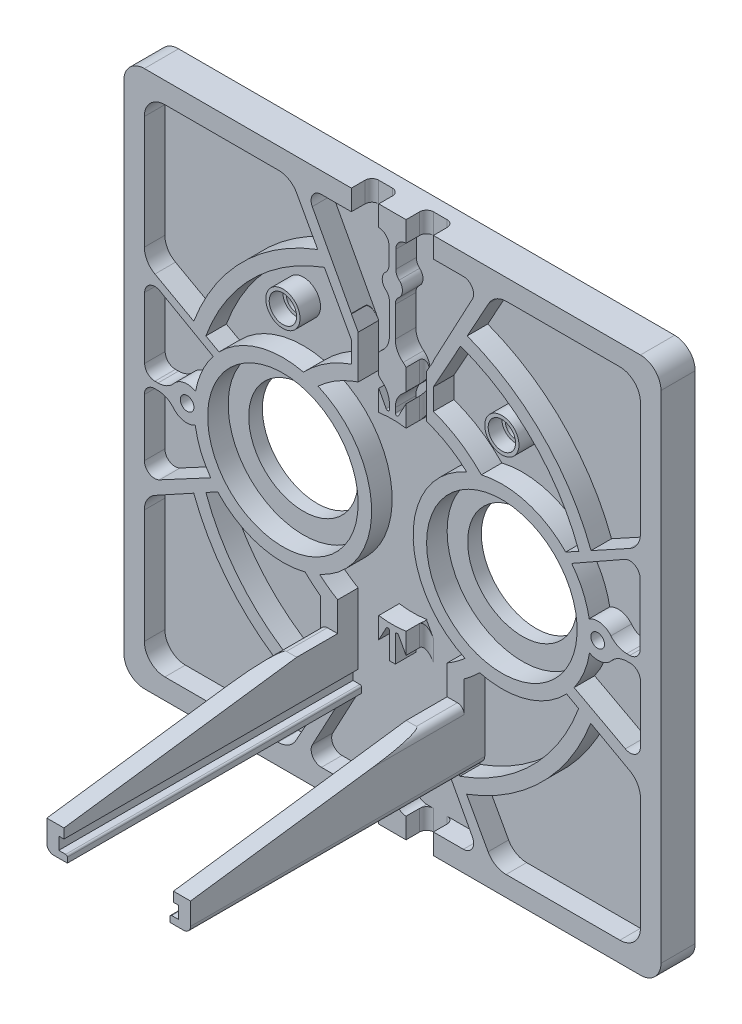
SolidWorks part; units mm, degrees
ref_plane "Спереди" through (0, 0, 0) normal (0, 0, 1) x (1, 0, 0)
ref_plane "Сверху" through (0, 0, 0) normal (0, 1, 0) x (1, 0, 0)
ref_plane "Справа" through (0, 0, 0) normal (1, 0, 0) x (0, 0, -1)
sketch "Эскиз1" plane through (0, 0, 0) normal (0, 0, 1) x (1, 0, 0)
  line L5 (-36.25, -39.25) -> (36.25, -39.25)
  line L6 (-39.25, -36.25) -> (-39.25, 36.25)
  line L7 (-36.25, 39.25) -> (36.25, 39.25)
  line L8 (39.25, -36.25) -> (39.25, 36.25)
  arc A0 (-36.25, -39.25) -> (-39.25, -36.25) centre (-36.25, -36.25) cw
  arc A1 (36.25, -39.25) -> (39.25, -36.25) centre (36.25, -36.25) ccw
  arc A2 (36.25, 39.25) -> (39.25, 36.25) centre (36.25, 36.25) cw
  arc A3 (-39.25, 36.25) -> (-36.25, 39.25) centre (-36.25, 36.25) cw
  dimension "D1" = 3
extrude "Бобышка-Вытянуть2" add sketch "Эскиз1" along normal blind 5
sketch "Эскиз6" plane through (0, 0, 5) normal (0, 0, 1) x (1, 0, 0)
  circle A0 centre (0, 0) radius 13
extrude "Вырез-Вытянуть2" cut sketch "Эскиз6" against normal blind 3
sketch "Эскиз10" plane through (0, 0, 5) normal (0, 0, 1) x (1, 0, 0)
  line L10 (-36.25, -33.25) -> (-36.25, -16.6195)
  line L11 (-33.25, -36.25) -> (-16.7128, -36.25)
  line L12 (-34.6933, -13.9895) -> (-12.8452, -2)
  line L13 (-14.0876, -34.7019) -> (-2, -12.8452)
  line L14 (-2, -12.8452) -> (-12.8452, -2)
  line L15 (36.2485, 33.2453) -> (36.2485, 16.6148)
  line L16 (33.2485, 36.2453) -> (16.7113, 36.2453)
  line L17 (34.6917, 13.9847) -> (12.8437, 1.9953)
  line L18 (14.086, 34.6972) -> (1.9985, 12.8405)
  line L19 (1.9985, 12.8405) -> (12.8437, 1.9953)
  line L20 (33.2453, -36.3173) -> (16.6148, -36.3173)
  line L21 (36.2453, -33.3173) -> (36.2453, -16.7802)
  line L22 (13.9847, -34.7606) -> (1.9953, -12.9126)
  line L23 (34.6972, -14.1549) -> (12.8405, -2.0673)
  line L24 (12.8405, -2.0673) -> (1.9953, -12.9126)
  line L25 (-33.25, 36.1811) -> (-16.6195, 36.1811)
  line L26 (-36.25, 33.1811) -> (-36.25, 16.644)
  line L27 (-13.9895, 34.6244) -> (-2, 12.7764)
  line L28 (-34.7019, 14.0187) -> (-12.8452, 1.9311)
  line L29 (-12.8452, 1.9311) -> (-2, 12.7764)
  circle A0 centre (0, 0) radius 13 construction
  arc A1 (-36.25, -16.6195) -> (-34.6933, -13.9895) centre (-33.25, -16.6195) cw
  arc A2 (-16.7128, -36.25) -> (-14.0876, -34.7019) centre (-16.7128, -33.25) ccw
  arc A3 (-36.25, -33.25) -> (-33.25, -36.25) centre (-33.25, -33.25) ccw
  arc A4 (36.2485, 16.6148) -> (34.6917, 13.9847) centre (33.2485, 16.6148) cw
  arc A5 (16.7113, 36.2453) -> (14.086, 34.6972) centre (16.7113, 33.2453) ccw
  arc A6 (36.2485, 33.2453) -> (33.2485, 36.2453) centre (33.2485, 33.2453) ccw
  arc A7 (16.6148, -36.3173) -> (13.9847, -34.7606) centre (16.6148, -33.3173) cw
  arc A8 (36.2453, -16.7802) -> (34.6972, -14.1549) centre (33.2453, -16.7802) ccw
  arc A9 (33.2453, -36.3173) -> (36.2453, -33.3173) centre (33.2453, -33.3173) ccw
  arc A10 (-16.6195, 36.1811) -> (-13.9895, 34.6244) centre (-16.6195, 33.1811) cw
  arc A11 (-36.25, 16.644) -> (-34.7019, 14.0187) centre (-33.25, 16.644) ccw
  arc A12 (-33.25, 36.1811) -> (-36.25, 33.1811) centre (-33.25, 33.1811) ccw
  point P34 (-36.25, -36.25)
  dimension "D1" = 3
extrude "Вырез-Вытянуть4" cut sketch "Эскиз10" against normal blind 3
sketch "Эскиз12" plane through (0, 0, 2) normal (0, 0, 1) x (1, 0, 0)
  circle A0 centre (0, 0) radius 18
  circle A1 centre (0, 0) radius 16
extrude "Бобышка-Вытянуть7" add sketch "Эскиз12" along normal blind 3
sketch "Эскиз18" plane through (0, 0, 2) normal (0, 0, 1) x (1, 0, 0)
  circle A0 centre (0, 0) radius 29
  circle A1 centre (0, 0) radius 31
extrude "Бобышка-Вытянуть10" add sketch "Эскиз18" along normal blind 3
sketch "Эскиз19" plane through (0, 0, 2) normal (0, 0, 1) x (1, 0, 0)
  circle A0 centre (-30, 0) radius 1
  circle A1 centre (30, 0) radius 1
extrude "Вырез-Вытянуть7" cut sketch "Эскиз19" against normal blind 2 and the other way blind 3
chamfer "Фаска6" distance 2 angle 45 2 edges at (-29, 0, 0) (31, 0, 0)
sketch "Эскиз21" plane through (0, 0, 5) normal (0, 0, 1) x (1, 0, 0)
  line L0 (-34.7046, 0.4543) -> (-34.2543, 0.4543)
  line L14 (-25.7046, 0.3762) -> (-13.9439, 0.3789)
  line L17 (-25.761, -0.4346) -> (-13.9898, -0.4346)
  line L18 (-33.9662, 12.24) -> (-13.8209, 0.8465)
  line L19 (-36.2046, 1.9543) -> (-36.2046, 10.9344)
  line L22 (-0.495, -34.7501) -> (-0.495, -32.2046)
  line L23 (-36.25, -2.0051) -> (-36.25, -10.3806)
  line L24 (-34.0421, -11.703) -> (-13.8718, -0.905)
  line L25 (-34.75, -0.5051) -> (-34.2952, -0.5051)
  line L26 (-0.4246, -27.7337) -> (-0.4246, -13.9898)
  line L27 (0.4345, -27.7337) -> (0.4345, -13.9898)
  line L28 (-11.693, -34.0421) -> (-0.895, -13.8718)
  line L29 (-1.995, -36.2501) -> (-10.3705, -36.2501)
  line L30 (2.005, -36.2501) -> (10.3805, -36.2501)
  line L31 (11.7029, -34.0421) -> (0.9049, -13.8718)
  line L32 (0.505, -34.7501) -> (0.505, -32.2046)
  line L38 (0.4928, 34.7538) -> (0.4928, 32.2084)
  line L44 (11.6908, 34.0458) -> (0.8928, 13.8756)
  line L45 (1.9928, 36.2538) -> (10.3683, 36.2538)
  line L46 (-2.0072, 36.2538) -> (-10.3827, 36.2538)
  line L47 (-11.7051, 34.0459) -> (-0.9071, 13.8756)
  line L48 (-0.5072, 34.7538) -> (-0.5072, 32.2084)
  line L50 (-0.4367, 13.9936) -> (-0.4367, 14.7298)
  line L51 (0.4224, 13.9936) -> (0.4224, 14.6764)
  line L52 (0.4224, 27.7375) -> (0.4224, 23.3236)
  line L53 (-0.4367, 27.7375) -> (-0.4367, 23.2702)
  line L54 (34.75, -0.5051) -> (34.2952, -0.5051)
  line L55 (36.25, -2.0051) -> (36.25, -10.3806)
  line L56 (34.0421, -11.703) -> (13.8718, -0.905)
  line L57 (25.761, -0.4346) -> (13.9898, -0.4346)
  line L58 (34.7046, 0.4543) -> (34.2543, 0.4543)
  line L59 (36.2046, 1.9543) -> (36.2046, 10.9344)
  line L60 (33.9662, 12.24) -> (13.8209, 0.8465)
  line L61 (25.7046, 0.3762) -> (13.9439, 0.3789)
  arc A8 (-12.855, 1.9365) -> (-12.8452, -2) centre (0, 0) ccw construction
  arc A9 (-12.855, 1.9365) -> (-12.8452, -2) centre (0, 0) ccw construction
  arc A15 (-36.25, -10.3806) -> (-34.0421, -11.703) centre (-34.75, -10.3806) ccw
  arc A16 (-36.25, -2.0051) -> (-34.75, -0.5051) centre (-34.75, -2.0051) cw
  arc A17 (-36.2046, 10.9344) -> (-33.9662, 12.24) centre (-34.7046, 10.9344) cw
  arc A18 (-36.2046, 1.9543) -> (-34.7046, 0.4543) centre (-34.7046, 1.9543) ccw
  arc A19 (-13.9898, -0.4346) -> (-13.8718, -0.905) centre (-13.9898, -0.6846) cw
  arc A20 (-13.9439, 0.3789) -> (-13.8209, 0.8465) centre (-13.944, 0.6289) ccw
  arc A22 (0.9636, -28.8771) -> (0.9985, -31.0924) centre (0.01, -30.0001) cw
  arc A23 (-0.9537, -28.8771) -> (-0.9886, -31.0924) centre (-0.0001, -30.0001) ccw
  arc A24 (-0.9886, -31.0924) -> (-0.495, -32.2046) centre (-1.995, -32.2046) cw
  arc A25 (-0.4246, -27.7337) -> (-0.9537, -28.8771) centre (-1.9246, -27.7337) cw
  arc A26 (0.4345, -27.7337) -> (0.9636, -28.8771) centre (1.9345, -27.7337) ccw
  arc A27 (0.9985, -31.0924) -> (0.505, -32.2046) centre (2.005, -32.2046) ccw
  arc A28 (10.3805, -36.2501) -> (11.7029, -34.0421) centre (10.3805, -34.7501) ccw
  arc A29 (2.005, -36.2501) -> (0.505, -34.7501) centre (2.005, -34.7501) cw
  arc A30 (-10.3705, -36.2501) -> (-11.693, -34.0421) centre (-10.3705, -34.7501) cw
  arc A31 (-1.995, -36.2501) -> (-0.495, -34.7501) centre (-1.995, -34.7501) ccw
  arc A32 (0.4345, -13.9898) -> (0.9049, -13.8718) centre (0.6845, -13.9898) cw
  arc A33 (-0.4246, -13.9898) -> (-0.895, -13.8718) centre (-0.6746, -13.9898) ccw
  arc A46 (-0.9658, 28.8809) -> (-1.0007, 31.0961) centre (-0.0122, 30.0038) cw
  arc A47 (0.9515, 28.8809) -> (0.9864, 31.0961) centre (-0.0021, 30.0038) ccw
  arc A48 (0.9864, 31.0961) -> (0.4928, 32.2084) centre (1.9928, 32.2084) cw
  arc A49 (0.4224, 27.7375) -> (0.9515, 28.8809) centre (1.9224, 27.7375) cw
  arc A50 (-0.4367, 27.7375) -> (-0.9658, 28.8809) centre (-1.9367, 27.7375) ccw
  arc A51 (-1.0007, 31.0961) -> (-0.5072, 32.2084) centre (-2.0072, 32.2084) ccw
  arc A52 (-10.3827, 36.2538) -> (-11.7051, 34.0459) centre (-10.3827, 34.7538) ccw
  arc A53 (-2.0072, 36.2538) -> (-0.5072, 34.7538) centre (-2.0072, 34.7538) cw
  arc A54 (10.3683, 36.2538) -> (11.6908, 34.0458) centre (10.3683, 34.7538) cw
  arc A55 (1.9928, 36.2538) -> (0.4928, 34.7538) centre (1.9928, 34.7538) ccw
  arc A56 (-0.4367, 13.9936) -> (-0.9071, 13.8756) centre (-0.6867, 13.9936) cw
  arc A57 (0.4224, 13.9936) -> (0.8928, 13.8756) centre (0.6724, 13.9936) ccw
  arc A60 (-1.542, 17.0558) -> (-1.542, 20.9442) centre (0.0417, 19) cw
  arc A61 (1.5709, 17.0369) -> (1.5709, 20.9631) centre (0.0311, 19) ccw
  arc A62 (0.4224, 14.6764) -> (1.5709, 17.0369) centre (3.4224, 14.6764) cw
  arc A63 (-0.4367, 14.7298) -> (-1.542, 17.0558) centre (-3.4367, 14.7298) ccw
  arc A64 (0.4224, 23.3236) -> (1.5709, 20.9631) centre (3.4224, 23.3236) ccw
  arc A65 (-0.4367, 23.2702) -> (-1.542, 20.9442) centre (-3.4367, 23.2702) cw
  arc A67 (-31.94, 1.5454) -> (-28.0541, 1.5099) centre (-30.0114, -0.0454) cw
  arc A68 (-31.9834, -1.5932) -> (-28.1042, -1.5612) centre (-30.0568, 0) ccw
  arc A69 (-25.7046, 0.3762) -> (-28.0541, 1.5099) centre (-25.7053, 3.3762) cw
  arc A70 (-25.761, -0.4346) -> (-28.1042, -1.5612) centre (-25.761, -3.4346) ccw
  arc A71 (-34.2952, -0.5051) -> (-31.9834, -1.5932) centre (-34.2952, -3.5051) cw
  arc A72 (-34.2543, 0.4543) -> (-31.94, 1.5454) centre (-34.2543, 3.4543) ccw
  arc A73 (36.25, -2.0051) -> (34.75, -0.5051) centre (34.75, -2.0051) ccw
  arc A74 (36.25, -10.3806) -> (34.0421, -11.703) centre (34.75, -10.3806) cw
  arc A75 (13.9898, -0.4346) -> (13.8718, -0.905) centre (13.9898, -0.6846) ccw
  arc A76 (25.761, -0.4346) -> (28.1042, -1.5612) centre (25.761, -3.4346) cw
  arc A77 (34.2952, -0.5051) -> (31.9834, -1.5932) centre (34.2952, -3.5051) ccw
  arc A78 (31.9834, -1.5932) -> (28.1042, -1.5612) centre (30.0568, 0) cw
  arc A79 (36.2046, 1.9543) -> (34.7046, 0.4543) centre (34.7046, 1.9543) cw
  arc A80 (36.2046, 10.9344) -> (33.9662, 12.24) centre (34.7046, 10.9344) ccw
  arc A81 (13.9439, 0.3789) -> (13.8209, 0.8465) centre (13.944, 0.6289) cw
  arc A82 (25.7046, 0.3762) -> (28.0541, 1.5099) centre (25.7053, 3.3762) ccw
  arc A83 (34.2543, 0.4543) -> (31.94, 1.5454) centre (34.2543, 3.4543) cw
  arc A84 (31.94, 1.5454) -> (28.0541, 1.5099) centre (30.0114, -0.0454) ccw
  point P39 (-12.9945, 0.3791)
  point P148 (0.4224, 16.5359)
  point P151 (-0.4367, 16.5384)
  dimension "D1" = 3
  dimension "D2" = 0.25
  dimension "D3" = 3
extrude "Вырез-Вытянуть8" cut sketch "Эскиз21" against normal blind 3
sketch "Эскиз22" plane through (0, 48.4151, 2) normal (0, 0, 1) x (1, 0, 0)
  line L52 (-8.75, -74.3614) -> (-7.75, -74.3614)
  line L53 (-8.75, -72.5614) -> (-8.75, -74.3614)
  line L58 (-10.5, -67.5575) -> (-10.5, -71.5614)
  line L59 (-10.5, -71.5614) -> (-10.5, -72.0614)
  line L60 (-10.5, -74.3614) -> (-10.5, -72.0614)
  line L64 (-8.75, -72.5614) -> (-8, -72.5614)
  line L65 (-9.5, -75.3614) -> (-7.5, -75.3614)
  line L66 (-7.5, -75.3614) -> (-7.5, -74.6114)
  line L67 (-9.5, -66.5575) -> (-8, -66.5575)
  line L68 (-8, -66.5575) -> (-8, -72.5614)
  line L70 (9.5, -66.5575) -> (8, -66.5575)
  line L71 (10.5, -67.5575) -> (10.5, -71.5614)
  line L72 (10.5, -71.5614) -> (10.5, -72.0614)
  line L73 (10.5, -74.3614) -> (10.5, -72.0614)
  line L74 (9.5, -75.3614) -> (7.5, -75.3614)
  line L75 (7.5, -75.3614) -> (7.5, -74.6114)
  line L76 (8.75, -74.3614) -> (7.75, -74.3614)
  line L77 (8.75, -72.5614) -> (8.75, -74.3614)
  line L78 (8.75, -72.5614) -> (8, -72.5614)
  line L79 (8, -66.5575) -> (8, -72.5614)
  arc A18 (9.5, -66.5575) -> (10.5, -67.5575) centre (9.5, -67.5575) cw
  arc A26 (-7.75, -74.3614) -> (-7.5, -74.6114) centre (-7.75, -74.6114) cw
  arc A29 (-9.5, -66.5575) -> (-10.5, -67.5575) centre (-9.5, -67.5575) ccw
  arc A30 (-9.5, -75.3614) -> (-10.5, -74.3614) centre (-9.5, -74.3614) cw
  arc A31 (9.5, -75.3614) -> (10.5, -74.3614) centre (9.5, -74.3614) ccw
  arc A32 (7.75, -74.3614) -> (7.5, -74.6114) centre (7.75, -74.6114) ccw
  point P0 (0, 0)
sketch "Эскиз27" plane through (0, -39.25, 0) normal (0, -1, 0) x (-1, 0, 0)
  line L15 (36.25, -5) -> (-36.25, -5) construction
  line L17 (1.995, -5) -> (5.9932, -5)
  line L22 (5.9932, -5) -> (5.9932, -3)
  line L23 (4.9932, -2) -> (2.995, -2)
  line L24 (1.995, -3) -> (1.995, -5)
  line L29 (-1.995, -3) -> (-1.995, -5)
  line L30 (-4.9932, -2) -> (-2.995, -2)
  line L31 (-5.9932, -5) -> (-5.9932, -3)
  line L32 (-1.995, -5) -> (-5.9932, -5)
  arc A0 (2.995, -2) -> (1.995, -3) centre (2.995, -3) ccw
  arc A1 (5.9932, -3) -> (4.9932, -2) centre (4.9932, -3) ccw
  arc A4 (-2.995, -2) -> (-1.995, -3) centre (-2.995, -3) cw
  arc A5 (-5.9932, -3) -> (-4.9932, -2) centre (-4.9932, -3) cw
  dimension "D1" = 1
extrude "Вырез-Вытянуть12" cut sketch "Эскиз27" against normal blind 78.5
sketch "Эскиз28" plane through (0, 0, 2) normal (0, 0, 1) x (1, 0, 0)
  line L0 (-5.9932, -14.8352) -> (-5.9932, -23.3951)
  line L1 (-5.9932, -23.3951) -> (-4.9932, -21.5271)
  line L2 (-4.9932, -21.5271) -> (-4.9932, -15.2009)
  line L3 (-4.9932, -15.2009) -> (-5.9932, -14.8352)
  line L4 (5.9932, -14.8352) -> (5.9932, -23.3765)
  line L5 (5.9932, -23.3765) -> (4.9932, -21.5085)
  line L6 (4.9932, -21.5085) -> (4.9932, -15.2009)
  line L7 (4.9932, -15.2009) -> (5.9932, -14.8352)
  line L8 (-4.9932, 15.2009) -> (-4.9932, 21.5081)
  line L9 (-4.9932, 21.5081) -> (-5.9932, 23.3125)
  line L10 (-5.9932, 23.3761) -> (-5.9932, 20.053) construction
  line L11 (-5.9932, 23.3125) -> (-5.9932, 14.8352)
  line L12 (-5.9932, 14.8352) -> (-4.9932, 15.2009)
  line L13 (5.9932, 14.8352) -> (5.9932, 23.3125)
  line L14 (5.9932, 23.4029) -> (5.9932, 20.0637) construction
  line L15 (5.9932, 23.3125) -> (4.9932, 21.535)
  line L16 (4.9932, 21.535) -> (4.9932, 15.2009)
  line L17 (4.9932, 15.2009) -> (5.9932, 14.8352)
  arc A0 (-4.9932, 15.2009) -> (-15.6201, 3.4658) centre (0, 0) ccw construction
  arc A1 (-4.9932, 15.2009) -> (-5.9932, 14.8352) centre (0, 0) ccw construction
extrude "Бобышка-Вытянуть12" add sketch "Эскиз28" along normal blind 3
extrude "Бобышка-Вытянуть15" add sketch "Эскиз22" along normal blind 43
sketch "Эскиз36" plane through (-10.5, 0, 0) normal (-1, 0, 0) x (0, 0, 1)
  line L0 (48, -17.3606) -> (5.1996, -17.3606)
  line L2 (48, -19.1424) -> (48, -25.9463) construction
  line L3 (48, -23.1435) -> (48, -17.3606)
  line L4 (5.1996, -17.3606) -> (48, -23.1435)
extrude "Вырез-Вытянуть13" cut sketch "Эскиз36" against normal blind 22
sketch "Эскиз43" plane through (0, 0, 5) normal (0, 0, 1) x (1, 0, 0)
  line L2 (-7.5, -26.1963) -> (-7.5, -26.9463)
  line L3 (-7.5, -26.9463) -> (7.5, -26.9463)
  line L4 (7.5, -26.9463) -> (7.5, -26.1963)
  line L8 (8, -24.1463) -> (8, -13.0041)
  line L9 (8, -13.0041) -> (4.2218, -15.0228)
  line L10 (4.2218, -15.0228) -> (2.995, -17.7761)
  line L11 (2.995, -17.7761) -> (-2.995, -17.7947)
  line L12 (-2.995, -17.7947) -> (-4.6348, -13.8953)
  line L13 (-4.6348, -13.8953) -> (-8, -12.9987)
  line L14 (-8, -12.9987) -> (-8, -24.1463)
  line L16 (-8, -24.1463) -> (-8.75, -24.1463)
  line L17 (-8.75, -24.1463) -> (-8.75, -25.9463)
  line L18 (-8.75, -25.9463) -> (-7.75, -25.9463)
  line L19 (8, -24.1463) -> (8.75, -24.1463)
  line L20 (8.75, -24.1463) -> (8.75, -25.9463)
  line L21 (8.75, -25.9463) -> (7.75, -25.9463)
  arc A0 (7.5, -26.1963) -> (7.75, -25.9463) centre (7.75, -26.1963) cw
  arc A1 (-7.75, -25.9463) -> (-7.5, -26.1963) centre (-7.75, -26.1963) cw
  dimension "D1" = 0.25
extrude "Вырез-Вытянуть17" cut sketch "Эскиз43" against normal blind 3
sketch "Эскиз45" plane through (0, 0, 2) normal (0, 0, 1) x (1, 0, 0)
  line L0 (-10.5, -19.1424) -> (-8, -19.1424)
  line L1 (-8, -18.1424) -> (-8, -23.1435) construction
  line L2 (-8, -19.1424) -> (-8, -16.1245)
  line L3 (-8, -16.1245) -> (-10.5, -13.7257)
  line L4 (-10.5, -13.7257) -> (-10.5, -19.1424)
  line L5 (10.5, -19.1424) -> (8, -19.1424)
  line L6 (8, -23.1435) -> (8, -18.1424) construction
  line L7 (8, -19.1424) -> (8, -16.1245)
  line L8 (8, -16.1245) -> (10.5, -13.7257)
  line L9 (10.5, -13.7257) -> (10.5, -19.1424)
extrude "Бобышка-Вытянуть14" add sketch "Эскиз45" along normal blind 3
sketch "Эскиз48" plane through (0, 0, 2) normal (0, 0, 1) x (1, 0, 0)
  circle A1 centre (-16, -0.1636) radius 8.0017
  circle A2 centre (16, 0) radius 8
sketch "Эскиз49" plane through (0, 0, 2) normal (0, 0, 1) x (1, 0, 0)
  line L0 (-28.7653, 2.1219) -> (-28.2607, 0.2317)
  line L1 (-28.2607, 0.2317) -> (-28.8124, -2.1683)
  line L3 (28.7653, 2.1219) -> (28.2607, 0.2317)
  line L4 (28.2607, 0.2317) -> (28.8124, -2.1683)
  arc A2 (-28.7653, 2.1219) -> (-28.8124, -2.1683) centre (-16, -0.1636) cw
  arc A3 (-28.0541, 1.5099) -> (-31.94, 1.5454) centre (-30.0114, -0.0454) ccw construction
  arc A4 (-31.9834, -1.5932) -> (-28.1042, -1.5612) centre (-30.0568, 0) ccw construction
  arc A5 (28.7653, 2.1219) -> (28.8124, -2.1683) centre (16, -0.1636) ccw
extrude "Бобышка-Вытянуть16" add sketch "Эскиз49" along normal blind 3
sketch "Эскиз50" plane through (0, 0, 2) normal (0, 0, 1) x (1, 0, 0)
  circle A0 centre (-16, -0.1636) radius 11
  circle A1 centre (16, -0.1636) radius 11
extrude "Вырез-Вытянуть18" cut sketch "Эскиз50" along normal blind 3
extrude "Вырез-Вытянуть19" cut sketch "Эскиз48" against normal blind 3
sketch "Эскиз51" plane through (0, 0, 2) normal (0, 0, 1) x (1, 0, 0)
  circle A0 centre (-16, 18.9767) radius 2.5
  circle A1 centre (16, 18.9767) radius 2.5
extrude "Бобышка-Вытянуть17" add sketch "Эскиз51" along normal blind 3
sketch "Эскиз53" plane through (0, 0, 5) normal (0, 0, 1) x (1, 0, 0)
  circle A0 centre (-16, 18.9767) radius 2
  circle A1 centre (16, 18.9767) radius 2
extrude "Вырез-Вытянуть21" cut sketch "Эскиз53" against normal blind 2
sketch "Эскиз54" plane through (0, 0, 3) normal (0, 0, 1) x (1, 0, 0)
  circle A0 centre (-16, 18.9767) radius 1.5
  circle A1 centre (16, 18.9767) radius 1.5
extrude "Вырез-Вытянуть22" cut sketch "Эскиз54" against normal blind 3
